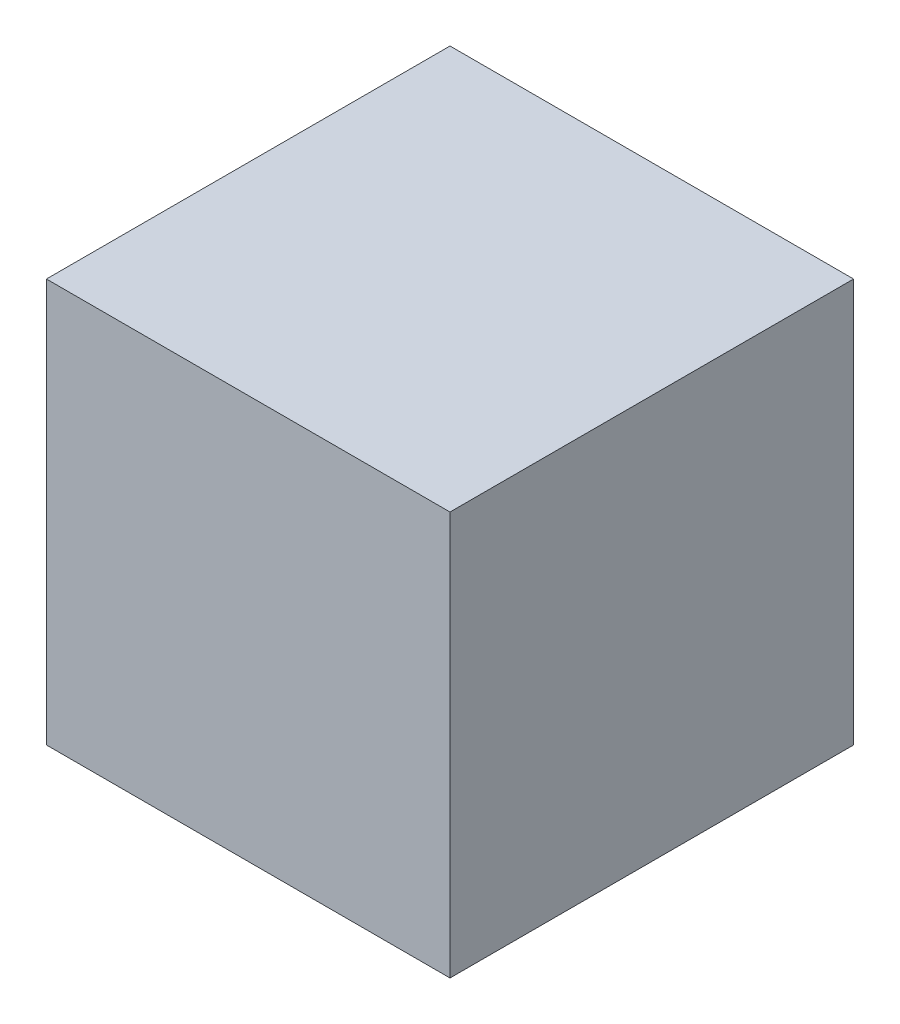
SolidWorks part; units mm, degrees
ref_plane "前视基准面" through (0, 0, 0) normal (0, 0, 1) x (1, 0, 0)
ref_plane "上视基准面" through (0, 0, 0) normal (0, 1, 0) x (1, 0, 0)
ref_plane "右视基准面" through (0, 0, 0) normal (1, 0, 0) x (0, 0, -1)
sketch "草图1" plane through (0, 0, 0) normal (0, 0, 1) x (1, 0, 0)
  line L1 (-52.8302, 37.7358) -> (47.1698, 37.7358)
  line L2 (-52.8302, 37.7358) -> (-52.8302, -62.2642)
  line L3 (-52.8302, -62.2642) -> (47.1698, -62.2642)
  line L4 (47.1698, 37.7358) -> (47.1698, -62.2642)
  dimension "D1" = 100
  dimension "D2" = 100
extrude "凸台-拉伸1" add sketch "草图1" along normal blind 100
